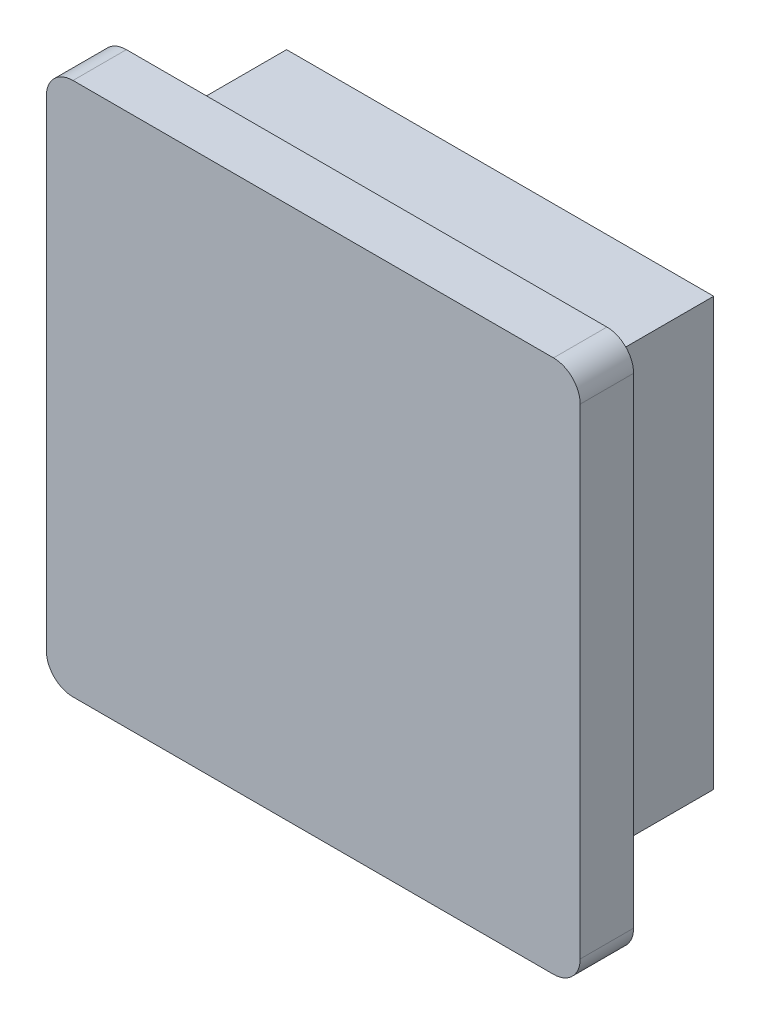
SolidWorks part; units mm, degrees
ref_plane "Płaszczyzna przednia" through (0, 0, 0) normal (0, 0, 1) x (1, 0, 0)
ref_plane "Płaszczyzna górna" through (0, 0, 0) normal (0, 1, 0) x (1, 0, 0)
ref_plane "Płaszczyzna prawa" through (0, 0, 0) normal (1, 0, 0) x (0, 0, -1)
sketch "Szkic1" plane through (0, 0, 0) normal (0, 0, 1) x (1, 0, 0)
  line L0 (2, 2) -> (2, 18)
  line L1 (0, 0) -> (20, 0)
  line L2 (0, 0) -> (0, 20)
  line L3 (0, 20) -> (20, 20)
  line L4 (20, 0) -> (20, 20)
  line L5 (2, 18) -> (18, 18)
  line L6 (18, 2) -> (18, 18)
  line L7 (2, 2) -> (18, 2)
  line L8 (3, 3) -> (3, 17)
  line L9 (3, 17) -> (17, 17)
  line L10 (17, 3) -> (17, 17)
  line L11 (3, 3) -> (17, 3)
  dimension "D1" = 2
  dimension "D2" = 1
extrude "Dodanie-wyciągnięcie1" add sketch "Szkic1" along normal blind 2 contours L8 L11 L10 L9 | L0 L7 L6 L5 L11 L8 L9 L10 | L1 L4 L3 L2 L7 L0 L5 L6 region at (2.2263, 10, 0) region at (0.2828, 10, 0) region at (10, 10, 0)
extrude "Dodanie-wyciągnięcie2" add sketch "Szkic1<4>" against normal blind 5 contours L0 L7 L6 L5 L11 L8 L9 L10 region at (2.2263, 10, 0)
sketch "Szkic1<4>" plane through (0, 0, 0) normal (0, 0, 1) x (1, 0, 0) same geometry as "Szkic1"
fillet "Zaokrąglenie1" radius 1 4 edges at (20, 0, 1) (0, 0, 1) (20, 20, 1) (0, 20, 1)
